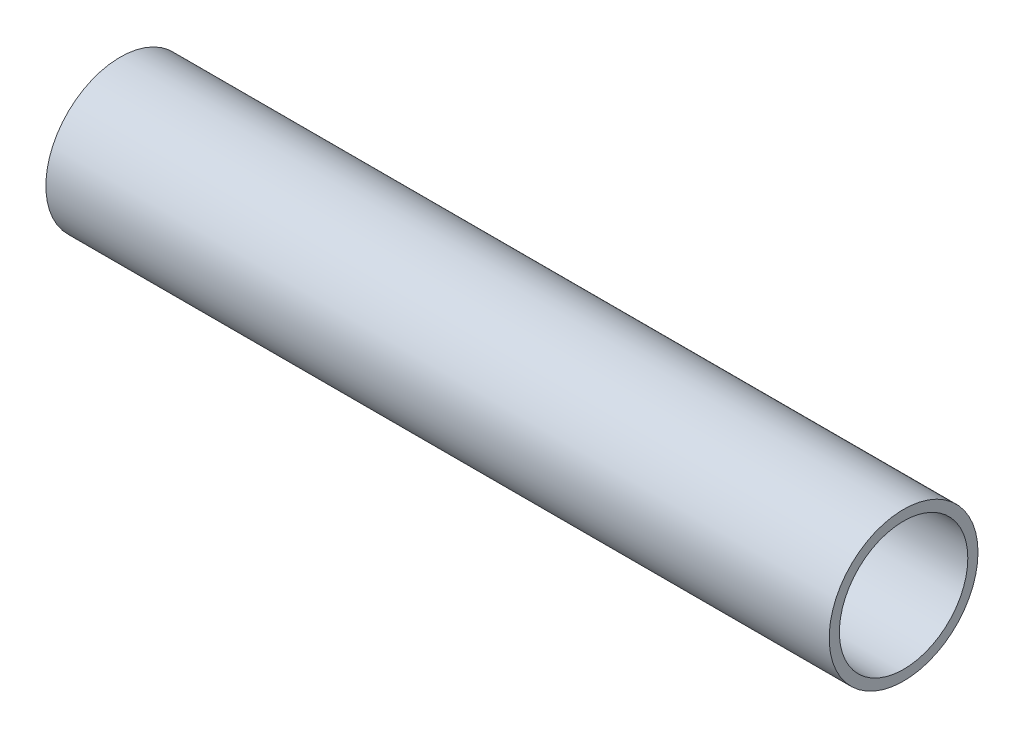
SolidWorks part; units mm, degrees
material "ABS PC"
ref_plane "Front Plane" through (0, 0, 0) normal (0, 0, 1) x (1, 0, 0)
ref_plane "Top Plane" through (0, 0, 0) normal (0, 1, 0) x (1, 0, 0)
ref_plane "Right Plane" through (0, 0, 0) normal (1, 0, 0) x (0, 0, -1)
sketch "Sketch1" plane through (0, 0, 0) normal (1, 0, 0) x (0, 0, -1)
  circle A0 centre (0, 0) radius 9.5
  circle A1 centre (0, 0) radius 8.2
  dimension "D1" = 1.3
  dimension "D2" = 19
extrude "Boss-Extrude1" add sketch "Sketch1" along normal blind 100
